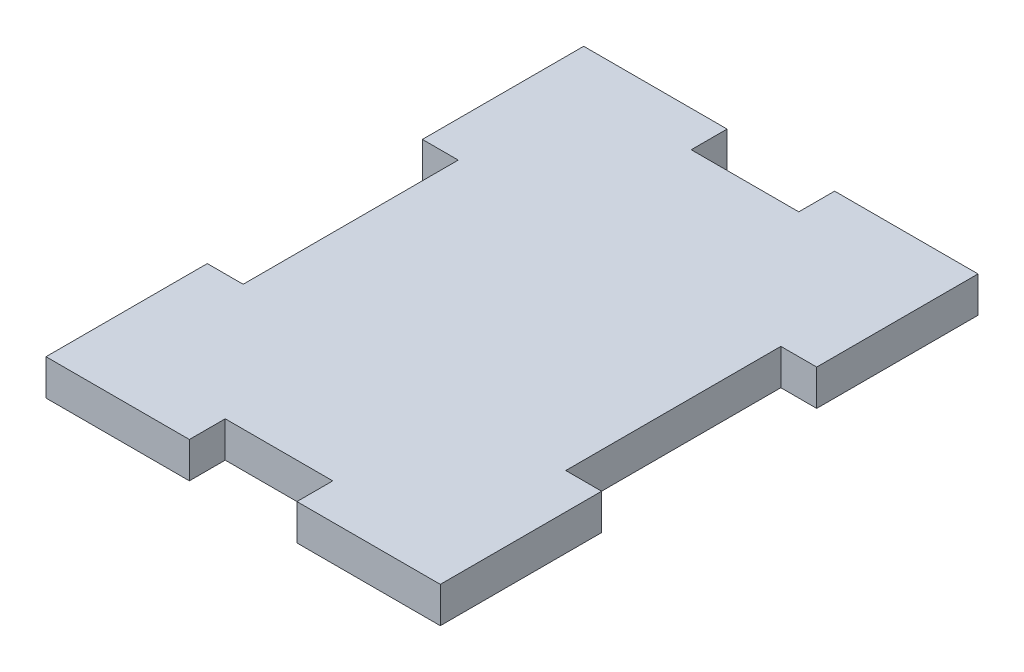
SolidWorks part; units mm, degrees
material "Acrylic (Medium-high impact)"
ref_plane "Front Plane" through (0, 0, 0) normal (0, 0, 1) x (1, 0, 0)
ref_plane "Top Plane" through (0, 0, 0) normal (0, 1, 0) x (1, 0, 0)
ref_plane "Right Plane" through (0, 0, 0) normal (1, 0, 0) x (0, 0, -1)
sketch "Sketch1" plane through (0, 0, 0) normal (0, 1, 0) x (1, 0, 0)
  line L1 (0, 0) -> (55, 0)
  line L2 (0, 0) -> (0, 75)
  line L3 (0, 75) -> (55, 75)
  line L4 (55, 0) -> (55, 75)
  dimension "D1" = 75
  dimension "D2" = 55
extrude "Boss-Extrude1" add sketch "Sketch1" along normal blind 5
sketch "Sketch3" plane through (0, 5, 0) normal (0, 1, 0) x (1, 0, 0)
  point P0 (15.5429, 20.9788)
sketch "Sketch5" plane through (0, 5, 0) normal (0, 1, 0) x (1, 0, 0)
  line L0 (0, 75) -> (0, 0) construction
  line L1 (0, 22.5) -> (5, 22.5)
  line L2 (0, 22.5) -> (0, 52.5)
  line L3 (0, 52.5) -> (5, 52.5)
  line L4 (5, 22.5) -> (5, 52.5)
  line L5 (55, 75) -> (0, 75) construction
  line L6 (35, 75) -> (20, 75)
  line L7 (35, 75) -> (35, 70)
  line L8 (35, 70) -> (20, 70)
  line L9 (20, 75) -> (20, 70)
  line L10 (55, 0) -> (55, 75) construction
  line L11 (55, 52.5) -> (50, 52.5)
  line L12 (55, 52.5) -> (55, 22.5)
  line L13 (55, 22.5) -> (50, 22.5)
  line L14 (50, 52.5) -> (50, 22.5)
  line L15 (0, 0) -> (55, 0) construction
  line L16 (20, 0) -> (35, 0)
  line L17 (20, 0) -> (20, 5)
  line L18 (20, 5) -> (35, 5)
  line L19 (35, 0) -> (35, 5)
  point P25 (0, 37.5)
  point P26 (27.5, 0)
  dimension "D1" = 5
  dimension "D2" = 30
  dimension "D3" = 15
extrude "Cut-Extrude3" cut sketch "Sketch5" against normal through all both and the other way through all
